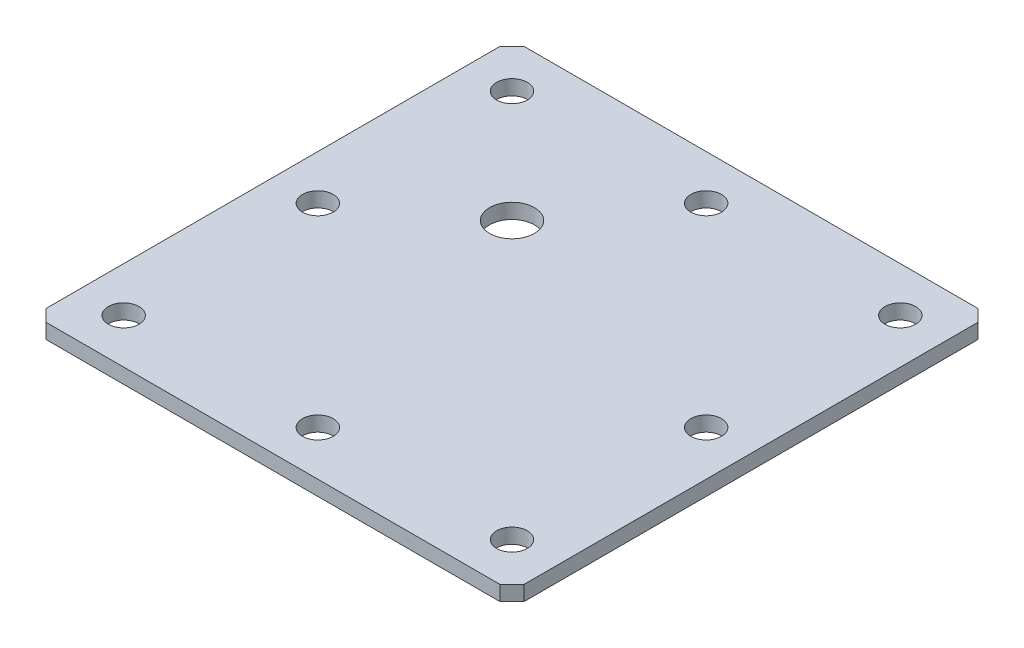
SolidWorks part; units mm, degrees
material "Rubber"
ref_plane "Front Plane" through (0, 0, 0) normal (0, 0, 1) x (1, 0, 0)
ref_plane "Top Plane" through (0, 0, 0) normal (0, 1, 0) x (1, 0, 0)
ref_plane "Right Plane" through (0, 0, 0) normal (1, 0, 0) x (0, 0, -1)
sketch "Sketch1" plane through (0, 0, 0) normal (0, 1, 0) x (1, 0, 0)
  line L0 (-49.428, 48.6342) -> (-46.888, 51.1742)
  line L1 (-46.888, -50.4258) -> (49.632, -50.4258)
  line L2 (-49.428, -47.8858) -> (-49.428, 48.6342)
  line L3 (-46.888, 51.1742) -> (49.632, 51.1742)
  line L4 (52.172, -47.8858) -> (52.172, 48.6342)
  line L5 (-49.428, -50.4258) -> (52.172, 51.1742) construction
  line L6 (-49.428, 51.1742) -> (52.172, -50.4258) construction
  line L7 (49.632, 51.1742) -> (52.172, 48.6342)
  line L8 (49.632, -50.4258) -> (52.172, -47.8858)
  line L9 (-49.428, -47.8858) -> (-46.888, -50.4258)
  line L10 (-39.903, 41.6492) -> (1.372, 41.6492)
  line L11 (42.647, -40.9008) -> (-39.903, -40.9008) construction
  line L12 (42.647, -40.9008) -> (42.647, 41.6492) construction
  line L13 (42.647, 41.6492) -> (-39.903, 41.6492) construction
  line L14 (-39.903, -40.9008) -> (-39.903, 41.6492) construction
  line L15 (42.647, -40.9008) -> (-39.903, 41.6492) construction
  line L16 (42.647, 41.6492) -> (-39.903, -40.9008) construction
  line L17 (42.647, -40.9008) -> (1.372, -40.9008)
  line L18 (-33.553, -34.5508) -> (36.297, -34.5508)
  line L19 (-33.553, -34.5508) -> (-33.553, 35.2992)
  line L20 (-33.553, 35.2992) -> (36.297, 35.2992)
  line L21 (36.297, -34.5508) -> (36.297, 35.2992)
  line L22 (-33.553, -34.5508) -> (36.297, 35.2992) construction
  line L23 (-33.553, 35.2992) -> (36.297, -34.5508) construction
  line L24 (-49.428, 17.8367) -> (-16.0905, 17.8367) construction
  line L25 (-16.0905, 17.8367) -> (-16.0905, 51.1742) construction
  circle A0 centre (-39.903, 41.6492) radius 3.2639
  circle A1 centre (1.372, 41.6492) radius 3.2639
  circle A2 centre (42.647, 41.6492) radius 3.2639
  circle A3 centre (42.647, 0.3742) radius 3.2639
  circle A4 centre (42.647, -40.9008) radius 3.2639
  circle A5 centre (1.372, -40.9008) radius 3.2639
  circle A6 centre (-39.903, -40.9008) radius 3.2639
  circle A7 centre (-39.903, 0.3742) radius 3.2639
  circle A9 centre (22.0095, -40.9008) radius 4.7625 construction
  circle A10 centre (-16.0905, 17.8367) radius 4.7625
  point P0 (1.372, 0.3742)
  point P13 (1.372, 0.3742)
  point P34 (1.372, 0.3742)
  dimension "D13" = 6.5278
  dimension "D14" = 9.525
  dimension "D1" = 101.6
  dimension "D2" = 101.6
  dimension "D3" = 2.54
  dimension "D4" = 2.54
  dimension "D5" = 2.54
  dimension "D6" = 2.54
  dimension "D7" = 2.54
  dimension "D8" = 2.54
  dimension "D9" = 2.54
  dimension "D10" = 2.54
  dimension "D11" = 82.55
  dimension "D12" = 82.55
  dimension "D15" = 69.85
  dimension "D16" = 69.85
  dimension "D17" = 33.3375
  dimension "D18" = 33.3375
extrude "Boss-Extrude1" add sketch "Sketch1" along normal blind 3.175 contours L18 L21 L20 L19 | L2 L9 L1 L8 L4 L7 L3 L0 A1 A0 A7 A6 A5 A4 A3 A2 L21 L18 L19 L20 region at (-47.142, 0, -48.8882) region at (1.6308, 0, -0.1154)
